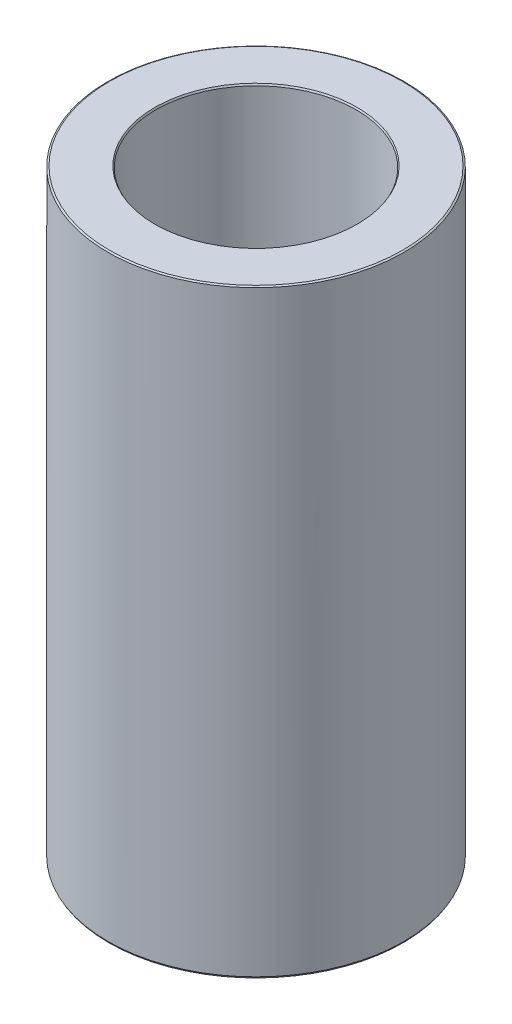
SolidWorks part; units mm, degrees
ref_plane "Front Plane" through (0, 0, 0) normal (0, 0, 1) x (1, 0, 0)
ref_plane "Top Plane" through (0, 0, 0) normal (0, 1, 0) x (1, 0, 0)
ref_plane "Right Plane" through (0, 0, 0) normal (1, 0, 0) x (0, 0, -1)
sketch "Sketch1" plane through (0, 0, 0) normal (0, 1, 0) x (1, 0, 0)
  circle A0 centre (0, 0) radius 40
  dimension "SLEEVE_OD" = 80
extrude "Boss-Extrude1" add sketch "Sketch1" along normal blind 161.9455
sketch "Sketch2" plane through (0, 0, 0) normal (0, 1, 0) x (1, 0, 0)
  circle A0 centre (0, 0) radius 27.1006
  dimension "BORE_D" = 54.2013
extrude "Cut-Extrude1" cut sketch "Sketch2" along normal through all
chamfer "Chamfer1" distance 0.2464 angle 60.945 4 edges at (0, 161.9455, 27.1006) (0, 0, 27.1006) (0, 0, 40) (0, 161.9455, 40) first distance on face at (0, 161.9455, 27.1006) first distance on face at (0, 0, 27.1006) first distance on face at (0, 161.9455, 40)
